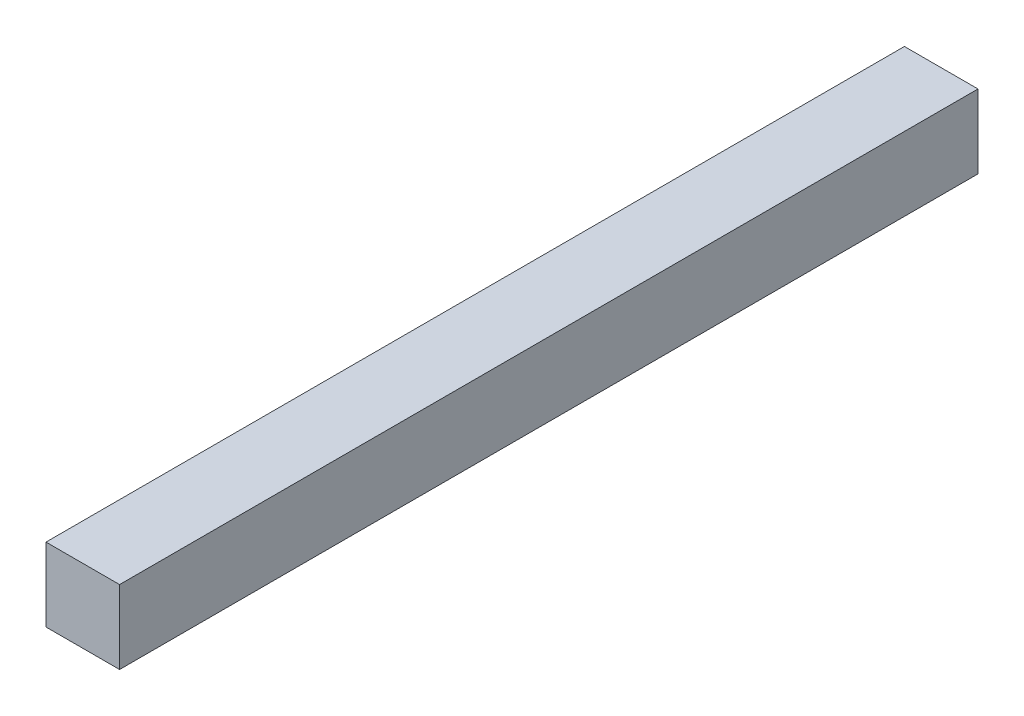
SolidWorks part; units mm, degrees
ref_plane "Front Plane" through (0, 0, 0) normal (0, 0, 1) x (1, 0, 0)
ref_plane "Top Plane" through (0, 0, 0) normal (0, 1, 0) x (1, 0, 0)
ref_plane "Right Plane" through (0, 0, 0) normal (1, 0, 0) x (0, 0, -1)
sketch "Sketch1" plane through (0, 0, 0) normal (0, 0, 1) x (1, 0, 0)
  line L1 (-15, -15) -> (15, -15)
  line L2 (-15, -15) -> (-15, 15)
  line L3 (-15, 15) -> (15, 15)
  line L4 (15, -15) -> (15, 15)
  line L5 (-15, -15) -> (15, 15) construction
  line L6 (-15, 15) -> (15, -15) construction
  point P0 (0, 0)
  dimension "D1" = 30
  dimension "D2" = 30
extrude "Boss-Extrude1" add sketch "Sketch1" along normal mid plane 350
